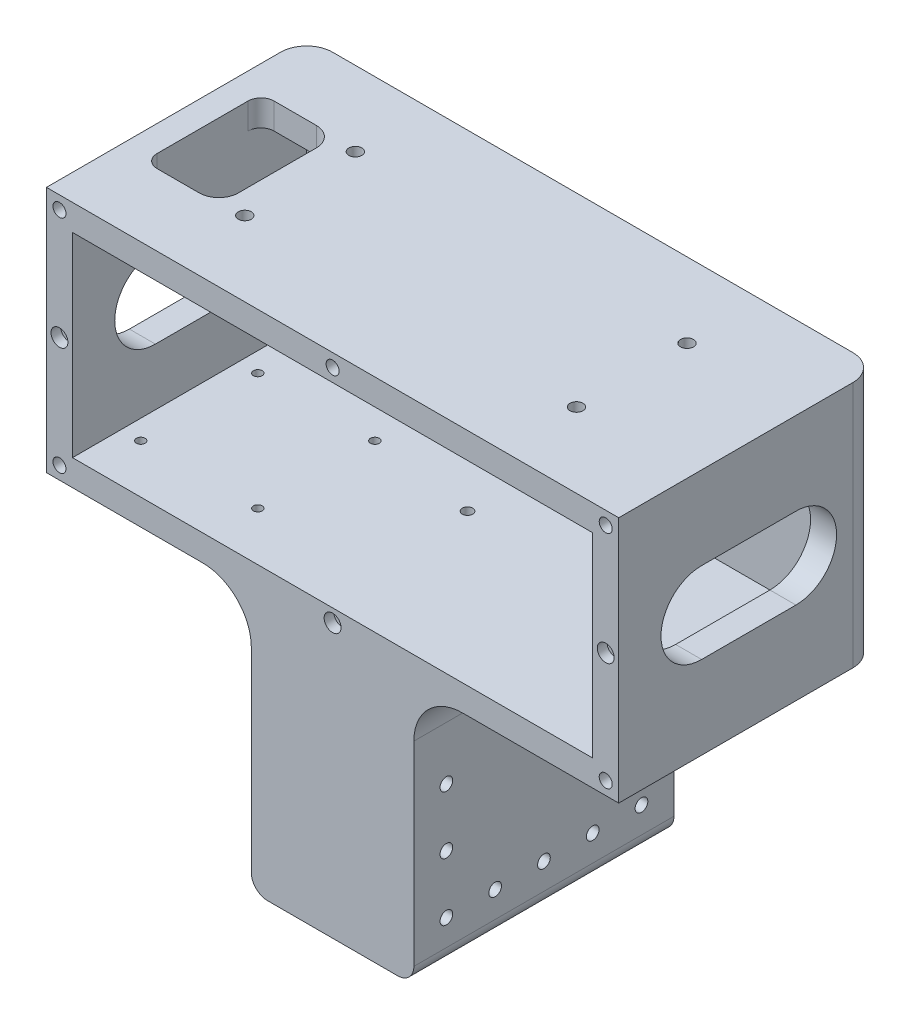
SolidWorks part; units mm, degrees
ref_plane "前视基准面" through (0, 0, 0) normal (0, 0, 1) x (1, 0, 0)
ref_plane "上视基准面" through (0, 0, 0) normal (0, 1, 0) x (1, 0, 0)
ref_plane "右视基准面" through (0, 0, 0) normal (1, 0, 0) x (0, 0, -1)
other "Configuration Table"
sketch "草图1" plane through (0, 0, 0) normal (0, 1, 0) x (1, 0, 0)
  line L1 (88, -40) -> (-88, -40)
  line L2 (88, -40) -> (88, 40)
  line L3 (88, 40) -> (-88, 40)
  line L4 (-88, -40) -> (-88, 40)
  line L5 (88, -40) -> (-88, 40) construction
  line L6 (88, 40) -> (-88, -40) construction
  point P0 (0, 0)
  dimension "D1" = 80
  dimension "D2" = 176
extrude "凸台-拉伸1" add sketch "草图1" along normal blind 76
sketch "草图3" plane through (0, 0, 40) normal (0, 0, 1) x (1, 0, 0)
  line L0 (-88, 0) -> (88, 0) construction
  line L1 (80, 8) -> (-80, 8)
  line L2 (80, 8) -> (80, 68)
  line L3 (80, 68) -> (-80, 68)
  line L4 (-80, 8) -> (-80, 68)
  line L5 (80, 8) -> (-80, 68) construction
  line L6 (80, 68) -> (-80, 8) construction
  line L7 (-88, 76) -> (-88, 0) construction
  line L8 (88, 76) -> (88, 0) construction
  line L9 (-88, 76) -> (88, 76) construction
  point P0 (0, 38)
  dimension "D1" = 8
  dimension "D2" = 8
  dimension "D3" = 8
  dimension "D4" = 8
extrude "切除-拉伸1" cut sketch "草图3" against normal offset from surface (72 mm away) 8 up to face at (0, 38, -40)
fillet "圆角1" radius 8 2 edges at (-88, 38, -40) (88, 38, -40)
sketch "草图5" plane through (0, 8, 0) normal (0, 1, 0) x (1, 0, 0)
  line L0 (-88, -40) -> (-88, 40) construction
  line L1 (-38, -25) -> (-74, -25) construction
  line L2 (-38, -25) -> (-38, 11) construction
  line L3 (-38, 11) -> (-74, 11) construction
  line L4 (-74, -25) -> (-74, 11) construction
  line L5 (-38, -25) -> (-74, 11) construction
  line L6 (-38, 11) -> (-74, -25) construction
  line L7 (-88, -40) -> (88, -40) construction
  line L8 (-74, -7) -> (-38, -7) construction
  line L9 (-56, -25) -> (-56, 11) construction
  circle A0 centre (-74, 11) radius 1.35
  circle A1 centre (-38, 11) radius 1.35
  circle A2 centre (-38, -25) radius 1.35
  circle A3 centre (-74, -25) radius 1.35
  point P0 (-56, -7)
  dimension "D4" = 2.7
  dimension "D1" = 14
  dimension "D2" = 36
  dimension "D3" = 36
  dimension "D5" = 15
extrude "切除-拉伸3" cut sketch "草图5" against normal through all
sketch "草图6" plane through (0, 76, 0) normal (0, 1, 0) x (1, 0, 0)
  line L0 (88, -40) -> (88, 32) construction
  line L1 (52, -17) -> (-50, -17) construction
  line L2 (52, -17) -> (52, 17) construction
  line L3 (52, 17) -> (-50, 17) construction
  line L4 (-50, -17) -> (-50, 17) construction
  line L5 (52, -17) -> (-50, 17) construction
  line L6 (52, 17) -> (-50, -17) construction
  line L7 (-88, -40) -> (88, -40) construction
  line L8 (1, 17) -> (1, -17) construction
  line L9 (-50, 0) -> (52, 0) construction
  line L10 (80, 40) -> (-80, 40) construction
  line L11 (-63, -12) -> (-63, 12) construction
  line L12 (-69, -12) -> (-69, 12)
  line L13 (-57, -12) -> (-57, 12)
  line L14 (-88, 32) -> (-88, -40) construction
  line L15 (-63, -18) -> (-76, -18)
  line L16 (-63, -18) -> (-63, 18)
  line L17 (-63, 18) -> (-76, 18)
  line L18 (-80, -14) -> (-80, 14)
  circle A0 centre (-50, 17) radius 2
  circle A1 centre (52, 17) radius 2
  circle A2 centre (52, -17) radius 2
  circle A3 centre (-50, -17) radius 2
  arc A4 (-69, -12) -> (-57, -12) centre (-63, -12) ccw
  arc A5 (-57, 12) -> (-69, 12) centre (-63, 12) ccw
  arc A6 (-76, -18) -> (-80, -14) centre (-76, -14) cw
  arc A7 (-76, 18) -> (-80, 14) centre (-76, 14) ccw
  point P0 (1, 0)
  point P20 (-63, 0)
  point P29 (-63, 18)
  point P30 (-63, -18)
  dimension "D4" = 4
  dimension "D10" = 4
  dimension "D1" = 36
  dimension "D2" = 34
  dimension "D3" = 102
  dimension "D5" = 13
  dimension "D6" = 12
  dimension "D7" = 22
  dimension "D8" = 22
  dimension "D9" = 8
extrude "切除-拉伸4" cut sketch "草图6" against normal up to surface (8 mm away) contours L17 A7 L18 A6 L15 A4 L12 A5 | L16 A5 L12 A4 | L13 A5 L16 A4 | A0 | A3 | A1 | A2 region at (-74.1606, 76, 0) region at (-65.8721, 76, 0) region at (-60.1279, 76, 0) region at (-50, 76, -17) region at (52, 76, -17) region at (52, 76, 17) region at (-50, 76, 17) up to face at (0, 68, 4)
sketch "草图7" plane through (0, 8, 0) normal (0, 1, 0) x (1, 0, 0)
  line L0 (70, 23) -> (70, -10) construction
  line L2 (88, -40) -> (88, 32) construction
  line L3 (-88, -40) -> (88, -40) construction
  circle A0 centre (70, 23) radius 1.6
  circle A1 centre (70, -10) radius 1.6
  circle A2 centre (-5, 6.5) radius 1.6
  point P6 (70, 6.5)
  dimension "D1" = 3.2
  dimension "D2" = 3.2
  dimension "D3" = 3.2
  dimension "D4" = 33
  dimension "D5" = 75
  dimension "D6" = 18
  dimension "D7" = 30
extrude "切除-拉伸5" cut sketch "草图7" against normal through all
sketch "草图8" plane through (0, 0, 0) normal (0, -1, 0) x (1, 0, 0)
  line L0 (-56, 25) -> (-56, -11) construction
  line L3 (-74, 7) -> (-38, 7) construction
  circle A0 centre (-74, 25) radius 2.5
  circle A1 centre (-38, 25) radius 2.5
  circle A2 centre (-38, -11) radius 2.5
  circle A3 centre (-74, -11) radius 2.5
  circle A4 centre (-5, -6.5) radius 3
  circle A5 centre (70, 10) radius 3
  circle A6 centre (70, -23) radius 3
  dimension "D1" = 5
  dimension "D2" = 6
  dimension "D3" = 6
  dimension "D4" = 6
extrude "切除-拉伸6" cut sketch "草图8" against normal blind 4
sketch "草图10" plane through (0, 0, -40) normal (0, 0, -1) x (-1, 0, 0)
  line L0 (-80, 27) -> (80, 27) construction
  line L1 (-80, 76) -> (-80, 0) construction
  line L2 (80, 0) -> (80, 76) construction
  line L3 (-80, 0) -> (80, 0) construction
  text T0 "XUANWU" font "Georgia" height 22
  dimension "D1" = 27
extrude "切除-拉伸8" cut sketch "草图10" against normal blind 2
sketch "草图11" plane through (0, 0, 40) normal (0, 0, 1) x (1, 0, 0)
  line L0 (-88, 76) -> (88, 76) construction
  line L1 (-88, 76) -> (-88, 0) construction
  line L2 (88, 76) -> (88, 0) construction
  circle A0 centre (-84, 72) radius 2
  circle A1 centre (-84, 4) radius 2
  circle A2 centre (84, 4) radius 2
  circle A3 centre (84, 72) radius 2
  circle A4 centre (0, 72) radius 2
  circle A5 centre (-84, 38) radius 2.6
  circle A6 centre (0, 4) radius 2.6
  circle A7 centre (84, 38) radius 2.6
  point P27 (-88, 38)
  point P28 (0, 76)
  dimension "D1" = 4
  dimension "D4" = 5.2
  dimension "D6" = 4
  dimension "D5" = 4
  dimension "D8" = 4
  dimension "D10" = 4
  dimension "D2" = 4
  dimension "D3" = 4
  dimension "D11" = 4
  dimension "D12" = 4
extrude "切除-拉伸9" cut sketch "草图11" against normal blind 8 contours A4 | A0 | A3 | A1 | A2
extrude "切除-拉伸10" cut sketch "草图11<3>" against normal blind 3 contours A5 | A6 | A7 region at (-84, 38, 40)
sketch "草图11<3>" plane through (0, 0, 40) normal (0, 0, 1) x (1, 0, 0) same geometry as "草图11"
sketch "Sketch1" plane through (-88, 0, 0) normal (-1, 0, 0) x (0, 0, 1)
  line L0 (14.5, 38) -> (-14.5, 38) construction
  line L1 (14.5, 25.5) -> (-14.5, 25.5)
  line L2 (14.5, 50.5) -> (-14.5, 50.5)
  line L4 (40, 0) -> (-40, 0) construction
  line L5 (40, 76) -> (40, 0) construction
  arc A0 (14.5, 25.5) -> (14.5, 50.5) centre (14.5, 38) ccw
  arc A1 (-14.5, 50.5) -> (-14.5, 25.5) centre (-14.5, 38) ccw
  point P2 (0, 38)
  point P7 (40, 38)
  point P14 (0, 0)
  point P15 (27, 38)
  dimension "D1" = 25
  dimension "D3" = 13
extrude "Cut-Extrude1" cut sketch "Sketch1" against normal through all
sketch "Sketch2" plane through (0, 0, -40) normal (0, 0, -1) x (-1, 0, 0)
  line L0 (-80, 0) -> (80, 0) construction
  line L1 (-25, 0) -> (25, 0)
  line L2 (-25, 0) -> (-25, -80)
  line L3 (-25, -80) -> (25, -80)
  line L4 (25, 0) -> (25, -80)
  point P6 (0, 0)
  dimension "D1" = 50
  dimension "D2" = 80
extrude "Boss-Extrude1" add sketch "Sketch2" against normal up to surface (80 mm away) up to face at (-81.4, 38, 40)
fillet "Fillet1" radius 15 2 edges at (25, 0, 0) (-25, 0, 0)
fillet "Fillet2" radius 5 2 edges at (25, -80, 0) (-25, -80, 0)
sketch "草图4" plane through (-25, 0, 0) normal (-1, 0, 0) x (0, 0, 1)
  line L0 (40, 76) -> (40, 0) construction
  line L7 (40, -80) -> (-40, -80) construction
  line L9 (30, -67) -> (-30, -67) construction
  line L10 (30, -67) -> (30, -31.4) construction
  line L11 (30, -31.4) -> (-30, -31.4) construction
  line L13 (-30, -67) -> (-30, -31.4) construction
  line L14 (30, -67) -> (-30, -31.4) construction
  line L15 (30, -31.4) -> (-30, -67) construction
  line L19 (-40, 0) -> (-40, 76) construction
  line L22 (-30, -49.2) -> (30, -49.2) construction
  line L23 (0, -31.4) -> (0, -67) construction
  circle A8 centre (-30, -31.4) radius 1.95
  circle A9 centre (30, -31.4) radius 1.95
  circle A10 centre (30, -67) radius 1.95
  circle A11 centre (-30, -67) radius 1.95
  circle A12 centre (-15, -67) radius 1.95
  circle A13 centre (0, -67) radius 1.95
  circle A14 centre (15, -67) radius 1.95
  circle A15 centre (-30, -49.2) radius 1.95
  circle A16 centre (30, -49.2) radius 1.95
  point P0 (0, -49.2)
  dimension "D5" = 3.9
  dimension "D6" = 4
  dimension "D1" = 13
  dimension "D2" = 10
  dimension "D3" = 10
  dimension "D4" = 35.6
  dimension "D7" = 2
extrude "切除-拉伸2" cut sketch "草图4" against normal blind 8
extrude "Cut-Extrude2" cut sketch "草图4<2>" along normal blind 8 from surface starting at face at (25, -45, 0)
sketch "草图4<2>" plane through (-25, 0, 0) normal (-1, 0, 0) x (0, 0, 1) same geometry as "草图4"
